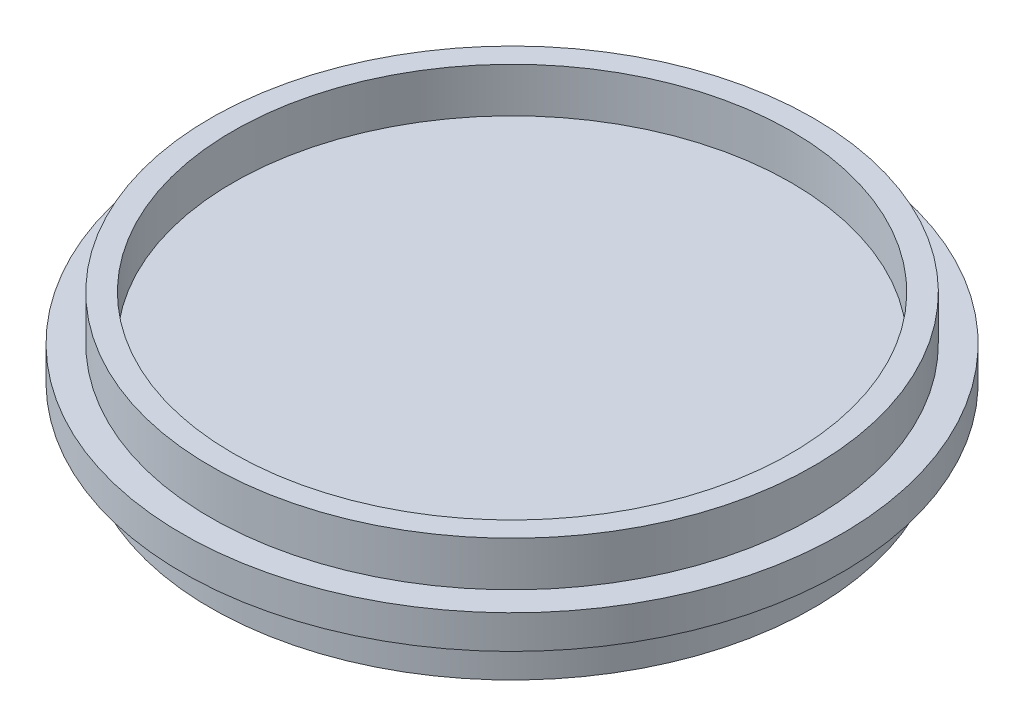
SolidWorks part; units mm, degrees
material "6061-T6 (SS)"
ref_plane "Front Plane" through (0, 0, 0) normal (0, 0, 1) x (1, 0, 0)
ref_plane "Top Plane" through (0, 0, 0) normal (0, 1, 0) x (1, 0, 0)
ref_plane "Right Plane" through (0, 0, 0) normal (1, 0, 0) x (0, 0, -1)
sketch "Sketch1" plane through (0, 0, 0) normal (0, 1, 0) x (1, 0, 0)
  line L5 (0, 0) -> (127.635, 0)
  line L6 (0, 0) -> (0, 127.635)
  line L7 (0, 127.635) -> (127.635, 127.635)
  line L8 (127.635, 0) -> (127.635, 127.635)
  dimension "D1" = 127.635
  dimension "D2" = 127.635
extrude "Boss-Extrude1" add sketch "Sketch1" along normal blind 9.525 contours L5 L8 L7 L6
sketch "Sketch12" plane through (0, 0, 0) normal (0, -1, 0) x (1, 0, 0)
  line L0 (63.8175, 0) -> (63.8175, -127.635) construction
  line L1 (0, 0) -> (127.635, 0) construction
  line L2 (0, -127.635) -> (127.635, -127.635) construction
  line L3 (0, -63.8175) -> (127.635, -63.8175) construction
  line L4 (0, 0) -> (0, -127.635) construction
  line L5 (127.635, 0) -> (127.635, -127.635) construction
  circle A0 centre (63.8175, -63.8175) radius 93.726
  dimension "D1" = 187.452
extrude "Boss-Extrude2" add sketch "Sketch12" against normal up to surface (9.525 mm away) contours A0 up to face at (63.8175, 9.525, -63.8175)
sketch "Sketch5" plane through (0, 9.525, 0) normal (0, 1, 0) x (1, 0, 0)
  circle A0 centre (63.8175, 63.8175) radius 46.355
  circle A3 centre (63.8175, 63.8175) radius 93.726 construction
  dimension "D1" = 92.71
extrude "Cut-Extrude1" [suppressed] cut sketch "Sketch5" against normal blind 9.525
sketch "Sketch11" [suppressed] plane through (0, 9.525, 0) normal (0, 1, 0) x (1, 0, 0)
  line L0 (63.8175, 63.8175) -> (63.8175, 115.443) construction
  circle A0 centre (63.8175, 115.443) radius 1.4351
  dimension "D2" = 2.8702
  dimension "D1" = 51.6255
extrude "Cut-Extrude3" [suppressed] cut sketch "Sketch11" against normal through all contours A0
pattern_circular "CirPattern1" [suppressed] count 12 over 360 of bodies 108
sketch "Sketch14" [suppressed] plane through (0, 9.525, 0) normal (0, -1, 0) x (1, 0, 0)
  line L0 (63.8175, -63.8175) -> (147.6375, -63.8175) construction
  line L1 (0, -19.2087) -> (0, 19.2087) construction
  line L2 (147.6375, -63.8175) -> (152.7175, -63.8175)
  line L3 (136.3808, -105.7742) -> (140.8401, -108.2104)
  circle A0 centre (63.8175, -63.8175) radius 46.355 construction
  arc A2 (147.6375, -63.8175) -> (136.3808, -105.7742) centre (63.8175, -63.8175) cw
  arc A3 (152.7175, -63.8175) -> (140.8401, -108.2104) centre (63.8175, -63.8175) cw
  point P0 (63.8175, -63.8175)
  dimension "D1" = 83.82
  dimension "D2" = 88.9
  dimension "D3" = 46.482
  dimension "D4" = 43.942
ref_plane "Support mirror reference plane" through (0, 4.7625, 0) normal (0, 1, 0) x (1, 0, 0)
sketch "Sketch25" [suppressed] plane through (0, 9.525, 0) normal (0, -1, 0) x (1, 0, 0)
  line L0 (63.8175, -63.8175) -> (123.0872, -4.5478) construction
  line L2 (123.0872, -4.5478) -> (126.6793, -0.9557)
  line L3 (144.7953, -42.1754) -> (149.6712, -40.7448)
  line L5 (63.8175, -63.8175) -> (147.6375, -63.8175) construction
  arc A2 (123.0872, -4.5478) -> (144.7953, -42.1754) centre (63.8175, -63.8175) cw
  arc A3 (126.6793, -0.9557) -> (149.6712, -40.7448) centre (63.8175, -63.8175) cw
  point P0 (63.8175, -63.8175)
  dimension "D1" = 83.82
  dimension "D2" = 88.9
  dimension "D3" = 46.482
  dimension "D4" = 43.942
  dimension "D5" = 45
sketch "Sketch30" plane through (0, 0, 0) normal (0, -1, 0) x (1, 0, 0)
  circle A0 centre (63.8175, -63.8175) radius 85.725
  circle A1 centre (63.8175, -63.8175) radius 79.375
  dimension "D1" = 171.45
  dimension "D2" = 158.75
extrude "Boss-Extrude3" add sketch "Sketch30" along normal blind 12.7
mirror "Mirror1" about plane through (0, 4.7625, 0) normal (0, 1, 0) of "Boss-Extrude3"
sketch "Sketch31" plane through (0, 0, 0) normal (0, -1, 0) x (-1, 0, 0)
  line L0 (-63.8175, -52.481) -> (-63.8175, 177.7216) construction
ref_plane "Plane1" through (0, 0, -149.5425) normal (0, 0, -1) x (-1, 0, 0)
ref_plane "Plane2" through (63.8175, 0, 0) normal (-1, 0, 0) x (0, 0, -1)
sketch "Sketch32" plane through (0, 0, -149.5425) normal (0, 0, -1) x (-1, 0, 0)
  line L4 (-63.8175, -87.3125) -> (-63.8175, 87.3125) construction
  line L5 (-149.5425, 0) -> (21.9075, 0) construction
  line L6 (21.9075, 9.525) -> (-149.5425, 9.525) construction
  circle A0 centre (-63.8175, -6.35) radius 1.4351
  circle A1 centre (-63.8175, 15.875) radius 1.4351
  dimension "D1" = 2.8702
  dimension "D2" = 2.8702
  dimension "D3" = 6.35
  dimension "D4" = 6.35
extrude "Cut-Extrude4" [suppressed] cut sketch "Sketch32" against normal blind 15.24
pattern_circular "CirPattern2" [suppressed] count 12 over 360 of bodies 125
